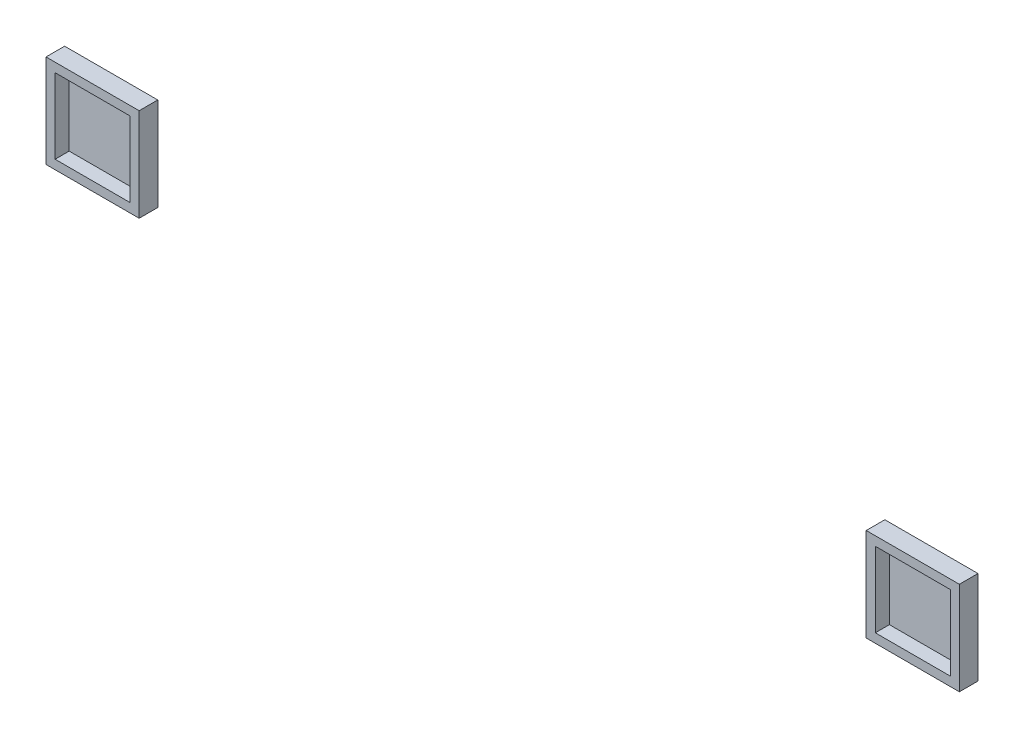
SolidWorks part; units mm, degrees
ref_plane "Front Plane" through (0, 0, 0) normal (0, 0, 1) x (1, 0, 0)
ref_plane "Top Plane" through (0, 0, 0) normal (0, 1, 0) x (1, 0, 0)
ref_plane "Right Plane" through (0, 0, 0) normal (1, 0, 0) x (0, 0, -1)
sketch "Sketch1" plane through (0, 0, 0) normal (0, 0, 1) x (1, 0, 0)
  line L1 (0, 0) -> (41.91, 0)
  line L2 (0, 0) -> (0, 41.91)
  line L3 (0, 41.91) -> (41.91, 41.91)
  line L4 (41.91, 0) -> (41.91, 41.91)
  line L5 (-5.08, 46.99) -> (46.99, 46.99)
  line L6 (-5.08, 46.99) -> (-5.08, -5.08)
  line L7 (-5.08, -5.08) -> (46.99, -5.08)
  line L8 (46.99, 46.99) -> (46.99, -5.08)
  line L9 (458.47, 41.91) -> (500.38, 41.91)
  line L10 (458.47, 41.91) -> (458.47, 0)
  line L11 (458.47, 0) -> (500.38, 0)
  line L12 (500.38, 41.91) -> (500.38, 0)
  line L13 (453.39, 46.99) -> (505.46, 46.99)
  line L14 (453.39, 46.99) -> (453.39, -5.08)
  line L15 (453.39, -5.08) -> (505.46, -5.08)
  line L16 (505.46, 46.99) -> (505.46, -5.08)
  point P17 (458.47, 20.955)
  dimension "D1" = 41.91
  dimension "D2" = 41.91
  dimension "D3" = 5.08
  dimension "D4" = 5.08
  dimension "D5" = 5.08
  dimension "D6" = 5.08
  dimension "D7" = 41.91
  dimension "D8" = 41.91
  dimension "D9" = 5.08
  dimension "D10" = 5.08
  dimension "D11" = 406.4
extrude "Boss-Extrude1" add sketch "Sketch1" along normal blind 7.874
sketch "Sketch2" plane through (0, 0, 0) normal (0, 0, -1) x (-1, 0, 0)
  line L0 (-46.99, 46.99) -> (5.08, 46.99) construction
  line L10 (-8.255, -5.08) -> (-8.255, -208.28)
  line L11 (-8.255, -208.28) -> (-33.655, -208.28)
  line L12 (-33.655, -5.08) -> (-33.655, -182.88)
  line L15 (-365.125, -208.28) -> (-390.525, -208.28)
  line L25 (-33.655, -208.28) -> (-365.125, -208.28)
  line L27 (-33.655, -182.88) -> (-365.125, -182.88)
  line L34 (-8.255, 46.99) -> (-8.255, 173.99)
  line L35 (-8.255, 173.99) -> (-33.655, 173.99)
  line L37 (-46.99, -5.08) -> (-46.99, 46.99) construction
  line L40 (-365.125, 173.99) -> (-391.5985, 173.99)
  line L54 (-33.655, 173.99) -> (-365.125, 173.99)
  line L55 (-33.655, 46.99) -> (-33.655, 148.59)
  line L56 (-33.655, 148.59) -> (-33.655, 46.99)
  line L57 (-466.725, 46.99) -> (-466.725, 148.59)
  line L58 (-365.125, 148.59) -> (-33.655, 148.59)
  line L59 (-505.46, 46.99) -> (-453.39, 46.99) construction
  line L61 (-8.255, 46.99) -> (-33.655, 46.99)
  line L62 (-8.255, -5.08) -> (-33.655, -5.08)
  line L63 (5.08, -5.08) -> (-46.99, -5.08) construction
  line L64 (-466.725, 148.59) -> (-365.125, 148.59)
  line L65 (-453.39, 46.99) -> (-453.39, -5.08) construction
  line L67 (-492.125, 46.99) -> (-492.125, 173.99)
  line L68 (-492.125, 173.99) -> (-391.5985, 173.99)
  line L69 (-466.725, 46.99) -> (-492.125, 46.99)
  line L70 (-466.725, -5.08) -> (-466.725, -182.88)
  line L71 (-453.39, -5.08) -> (-505.46, -5.08) construction
  line L72 (-466.725, -182.88) -> (-365.125, -182.88)
  line L73 (-492.125, -5.08) -> (-492.125, -208.28)
  line L74 (-492.125, -208.28) -> (-390.525, -208.28)
  line L75 (-466.725, -5.08) -> (-492.125, -5.08)
  dimension "D1" = 203.2
  dimension "D2" = 25.4
  dimension "D3" = 127
  dimension "D4" = 25.4
  dimension "D5" = 13.335
  dimension "D6" = 101.6
  dimension "D7" = 0
  dimension "D8" = 25.4
  dimension "D9" = 25.4
  dimension "D10" = 331.47
  dimension "D11" = 127
  dimension "D12" = 25.4
  dimension "D13" = 13.335
sketch "Sketch3" plane through (0, 0, 0) normal (0, 0, -1) x (-1, 0, 0)
  line L1 (5.08, -5.08) -> (-46.99, -5.08)
  line L2 (5.08, -5.08) -> (5.08, 46.99)
  line L3 (5.08, 46.99) -> (-46.99, 46.99)
  line L4 (-46.99, -5.08) -> (-46.99, 46.99)
  line L5 (-453.39, -5.08) -> (-505.46, -5.08)
  line L6 (-453.39, -5.08) -> (-453.39, 46.99)
  line L7 (-453.39, 46.99) -> (-505.46, 46.99)
  line L8 (-505.46, -5.08) -> (-505.46, 46.99)
extrude "Boss-Extrude6" add sketch "Sketch3" along normal blind 2.54
